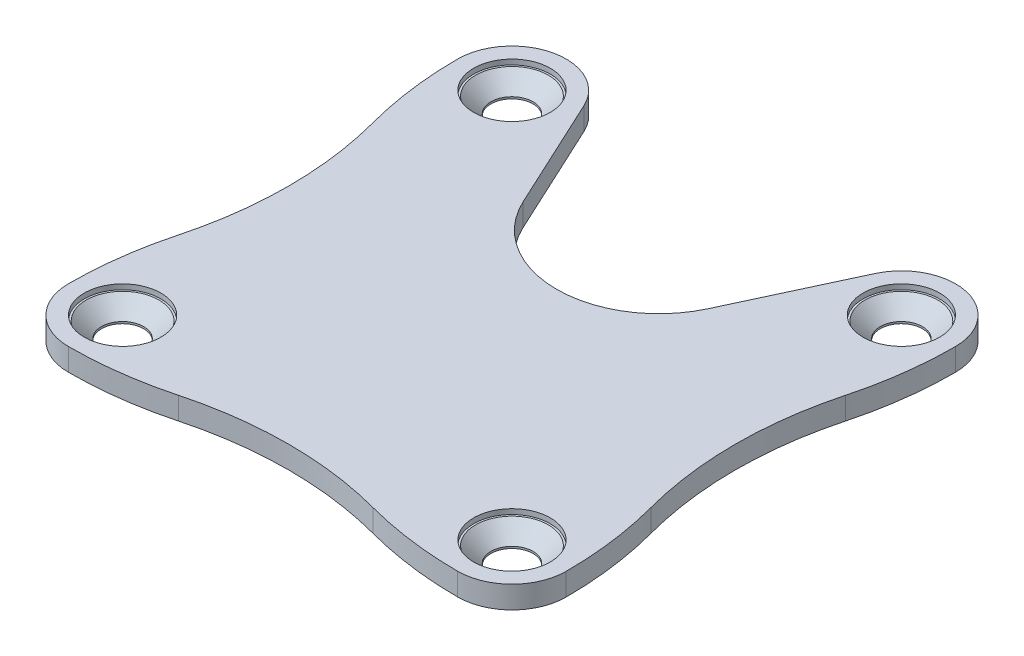
SolidWorks part; units mm, degrees
ref_plane "Front Plane" through (0, 0, 0) normal (0, 0, 1) x (1, 0, 0)
ref_plane "Top Plane" through (0, 0, 0) normal (0, 1, 0) x (1, 0, 0)
ref_plane "Right Plane" through (0, 0, 0) normal (1, 0, 0) x (0, 0, -1)
sketch "Sketch1" plane through (0, 0, 0) normal (0, 1, 0) x (1, 0, 0)
  line L0 (0, 19.5) -> (0, -19.5) construction
  line L1 (-19.5, 19.5) -> (19.5, 19.5)
  line L2 (-19.5, 19.5) -> (-19.5, -19.5)
  line L3 (-19.5, -19.5) -> (19.5, -19.5)
  line L4 (19.5, 19.5) -> (19.5, -19.5)
  line L5 (-19.5, 19.5) -> (19.5, -19.5) construction
  line L6 (-19.5, -19.5) -> (19.5, 19.5) construction
  line L7 (-19.5, 35.2) -> (-19.5, -19.5) construction
  circle A0 centre (-15.25, 15.25) radius 1.65
  circle A1 centre (15.25, 15.25) radius 1.65
  circle A2 centre (-15.25, -15.25) radius 1.65
  circle A3 centre (15.25, -15.25) radius 1.65
  circle A4 centre (15.25, 15.25) radius 1.65 construction
  circle A5 centre (15.25, -15.25) radius 1.65 construction
  circle A6 centre (-15.25, -15.25) radius 1.65 construction
  circle A7 centre (-15.25, 15.25) radius 1.65 construction
  point P0 (0, 0)
extrude "Shape" add sketch "Sketch1" along normal blind 1.75
sketch "Sketch2" plane through (0, 1.75, 0) normal (0, 1, 0) x (1, 0, 0)
  line L0 (0, 19.5) -> (0, -19.5) construction
  line L2 (-15.25, 16.9) -> (-15.25, -16.9) construction
  line L3 (-15.25, 0) -> (-19.5, 0) construction
  line L4 (-19.5, 19.5) -> (-19.5, -19.5) construction
  line L5 (19.5, 19.5) -> (-19.5, 19.5) construction
  line L6 (-19.5, -19.5) -> (19.5, -19.5) construction
  line L7 (-15.25, 0) -> (-11, 0) construction
  line L8 (-7.2551, 8.1291) -> (-12.5383, 19.5)
  line L9 (7.2551, 8.1291) -> (12.5383, 19.5)
  line L10 (-12.5383, 19.5) -> (12.5383, 19.5)
  line L14 (19.5, -19.5) -> (19.5, 19.5)
  line L15 (19.5, 19.5) -> (-19.5, 19.5)
  line L16 (-19.5, 19.5) -> (-19.5, -19.5)
  line L17 (-19.5, -19.5) -> (19.5, -19.5)
  line L18 (19.5, -19.5) -> (19.5, 19.5)
  line L19 (19.5, 19.5) -> (-19.5, 19.5)
  line L20 (-19.5, 19.5) -> (-19.5, -19.5)
  line L21 (-19.5, -19.5) -> (19.5, -19.5)
  circle A0 centre (0, 11.5) radius 8
  circle A1 centre (-15.25, 15.25) radius 1.65 construction
  circle A2 centre (-15.25, -15.25) radius 1.65 construction
  circle A3 centre (-15.25, 15.25) radius 4.25
  circle A4 centre (15.25, 15.25) radius 4.25
  circle A5 centre (-15.25, -15.25) radius 4.25
  circle A6 centre (15.25, -15.25) radius 4.25
  line M3 (19.5, -19.5) -> (19.5, 19.5)
  line M4 (19.5, 19.5) -> (-19.5, 19.5)
  line M5 (-19.5, 19.5) -> (-19.5, -19.5)
  line M6 (-19.5, -19.5) -> (19.5, -19.5)
  dimension "D1" = 16
  dimension "D2" = 0
extrude "Camera cut" cut sketch "Sketch2" against normal up to next contours A0 L10 L8 | A0 | A0 L9 M4 | A3 L8 M4 | A4 L9 M4 | A3 L19 M5 | A4 L18 M4 | A6 M6 M3 | A5 M5 M6 region at (0, 1.75, -11.5) region at (-8.2479, 1.75, -16.7625) region at (-12.8704, 1.75, -18.9795) region at (8.2479, 1.75, -16.7625) region at (-18.5507, 1.75, -18.5507) region at (12.8704, 1.75, -18.9795) region at (18.5507, 1.75, -18.5507) region at (-18.5507, 1.75, 18.5507) region at (18.5507, 1.75, 18.5507)
sketch "Sketch4" plane through (0, 1.75, 0) normal (0, 1, 0) x (1, 0, 0)
  circle A0 centre (-15.25, 15.25) radius 3
  circle A1 centre (15.25, 15.25) radius 3
  circle A2 centre (15.25, -15.25) radius 3
  circle A3 centre (-15.25, -15.25) radius 3
  dimension "D1" = 6
extrude "Screw head cuts" cut sketch "Sketch4" against normal blind 0.4
chamfer "Screw head chamfers" distance 1.2 angle 45 4 edges at (-15.25, 1.35, 16.9) (15.25, 1.35, 16.9) (15.25, 1.35, -13.6) (-15.25, 1.35, -13.6)
sketch "Sketch5" plane through (0, 1.75, 0) normal (0, 1, 0) x (1, 0, 0)
  line L0 (-19.5, 15.25) -> (19.5, 15.25) construction
  line L1 (-19.5, -15.25) -> (19.5, -15.25) construction
  line L2 (0, -19.5) -> (0, 15.25) construction
  line L3 (-15.25, -19.5) -> (15.25, -19.5) construction
  line L4 (-17.5, 18.8556) -> (-17.5, -18.8556) construction
  line L5 (-19.5, 15.25) -> (-19.5, -15.25) construction
  line L6 (-17.5, 0) -> (0, 0) construction
  line L7 (-18.5, 17.9886) -> (-18.5, -17.9886) construction
  line L8 (-18.5, 0) -> (-17.5, 0) construction
  line L9 (-18.5, 0) -> (-19.5, 0) construction
  line L10 (-17.5, 0) -> (-19.5, 15.25) construction
  line L11 (-15.25, 15.25) -> (15.25, -15.25) construction
  line L12 (-18.5, 7.625) -> (-17.5, 7.625) construction
  line L13 (-19.5, 15.25) -> (-19.5, -15.25)
  line L14 (-15.25, -19.5) -> (15.25, -19.5)
  line L15 (19.5, -15.25) -> (19.5, 15.25)
  arc A0 (-19.5, -15.25) -> (-15.25, -19.5) centre (-15.25, -15.25) ccw construction
  arc A1 (-11.3957, 17.0408) -> (-19.5, 15.25) centre (-15.25, 15.25) ccw construction
  arc A2 (-19.5, 15.25) -> (-18.5, 7.625) centre (10.0703, 15.25) ccw
  arc A3 (-18.5, 7.625) -> (-18.5, -7.625) centre (-47.0703, 0) cw
  arc A4 (-19.5, -15.25) -> (-18.5, -7.625) centre (10.0703, -15.25) cw
  arc A5 (19.5, -15.25) -> (18.5, -7.625) centre (-10.0703, -15.25) ccw
  arc A6 (18.5, 7.625) -> (18.5, -7.625) centre (47.0703, 0) ccw
  arc A7 (19.5, 15.25) -> (18.5, 7.625) centre (-10.0703, 15.25) cw
  arc A8 (15.25, -19.5) -> (7.625, -18.5) centre (15.25, 10.0703) cw
  arc A9 (-7.625, -18.5) -> (7.625, -18.5) centre (0, -47.0703) cw
  arc A10 (-15.25, -19.5) -> (-7.625, -18.5) centre (-15.25, 10.0703) ccw
  dimension "D1" = 2
extrude "Beauty cuts" cut sketch "Sketch5" against normal up to next
